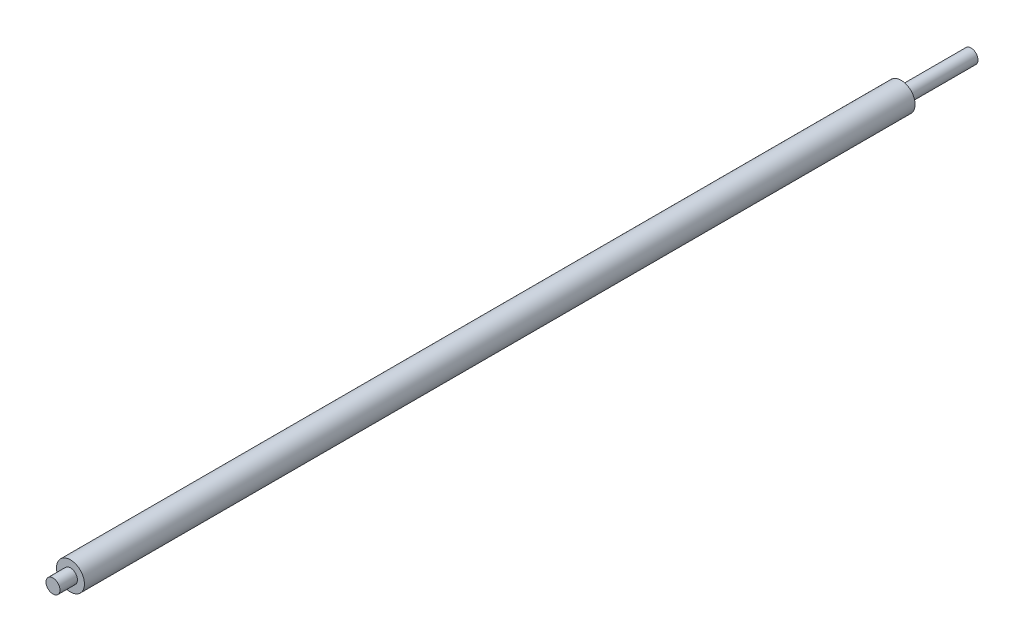
SolidWorks part; units mm, degrees
ref_plane "Front Plane" through (0, 0, 0) normal (0, 0, 1) x (1, 0, 0)
ref_plane "Top Plane" through (0, 0, 0) normal (0, 1, 0) x (1, 0, 0)
ref_plane "Right Plane" through (0, 0, 0) normal (1, 0, 0) x (0, 0, -1)
sketch "Sketch1" plane through (0, 0, 0) normal (0, 0, 1) x (1, 0, 0)
  circle A0 centre (0, 0) radius 6
  dimension "D1" = 12
extrude "Boss-Extrude1" add sketch "Sketch1" along normal mid plane 356.5
sketch "Sketch2" plane through (0, 0, 178.25) normal (0, 0, 1) x (1, 0, 0)
  circle A0 centre (0, 0) radius 3
  dimension "D1" = 6
extrude "Boss-Extrude2" add sketch "Sketch2" along normal blind 7.5
sketch "Sketch3" plane through (0, 0, -178.25) normal (0, 0, -1) x (-1, 0, 0)
  circle A0 centre (0, 0) radius 3
  dimension "D1" = 6
extrude "Boss-Extrude3" add sketch "Sketch3" along normal blind 30
